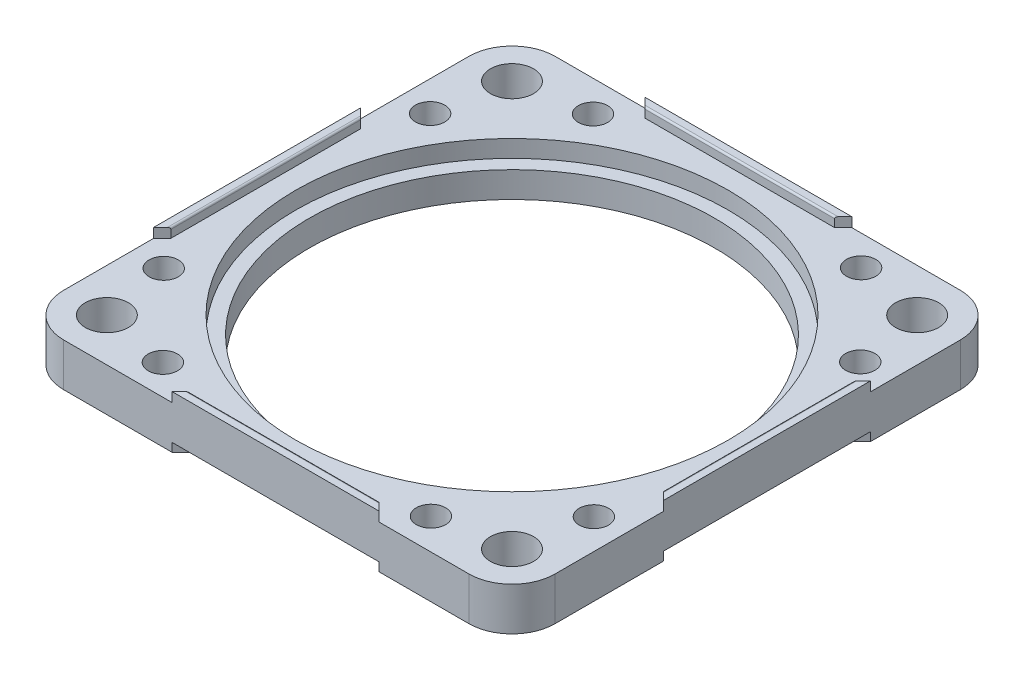
SolidWorks part; units mm, degrees
note: The reader was unsure of these and kept them because the rebuilt part matched: shared geometry of "Sketch5<3>".
material "PLA"
ref_plane "Front Plane" through (0, 0, 0) normal (0, 0, 1) x (1, 0, 0)
ref_plane "Top Plane" through (0, 0, 0) normal (0, 1, 0) x (1, 0, 0)
ref_plane "Right Plane" through (0, 0, 0) normal (1, 0, 0) x (0, 0, -1)
sketch "Sketch1" plane through (0, 0, 0) normal (0, 1, 0) x (1, 0, 0)
  line L1 (23.5, -28.5) -> (-23.5, -28.5)
  line L2 (28.5, -23.5) -> (28.5, 23.5)
  line L3 (23.5, 28.5) -> (-23.5, 28.5)
  line L4 (-28.5, -23.5) -> (-28.5, 23.5)
  line L5 (28.5, -28.5) -> (-28.5, 28.5) construction
  line L6 (28.5, 28.5) -> (-28.5, -28.5) construction
  arc A0 (28.5, -23.5) -> (23.5, -28.5) centre (23.5, -23.5) cw
  arc A1 (28.5, 23.5) -> (23.5, 28.5) centre (23.5, 23.5) ccw
  arc A2 (-28.5, 23.5) -> (-23.5, 28.5) centre (-23.5, 23.5) cw
  arc A3 (-28.5, -23.5) -> (-23.5, -28.5) centre (-23.5, -23.5) ccw
  point P0 (0, 0)
  dimension "D3" = 5
  dimension "D1" = 57
  dimension "D2" = 57
extrude "Boss-Extrude1" add sketch "Sketch1" along normal blind 5
sketch "Sketch2" plane through (0, 5, 0) normal (0, 1, 0) x (1, 0, 0)
  line L4 (28.5, -23.5) -> (28.5, 23.5)
  line L5 (23.5, 28.5) -> (-23.5, 28.5)
  line L6 (-28.5, 23.5) -> (-28.5, -23.5)
  line L7 (-23.5, -28.5) -> (23.5, -28.5)
  line L8 (28.5, -23.5) -> (28.5, 23.5)
  line L9 (23.5, 28.5) -> (-23.5, 28.5)
  line L10 (-28.5, 23.5) -> (-28.5, -23.5)
  line L11 (-23.5, -28.5) -> (23.5, -28.5)
  circle A0 centre (23.5, 23.5) radius 2.5
  circle A1 centre (15.5, 25) radius 1.7
  circle A2 centre (24.9, 15.5) radius 1.7
  arc A4 (23.5, -28.5) -> (28.5, -23.5) centre (23.5, -23.5) ccw
  arc A5 (28.5, 23.5) -> (23.5, 28.5) centre (23.5, 23.5) ccw
  arc A6 (-23.5, 28.5) -> (-28.5, 23.5) centre (-23.5, 23.5) ccw
  arc A7 (-28.5, -23.5) -> (-23.5, -28.5) centre (-23.5, -23.5) ccw
  arc A8 (23.5, -28.5) -> (28.5, -23.5) centre (23.5, -23.5) ccw
  arc A9 (28.5, 23.5) -> (23.5, 28.5) centre (23.5, 23.5) ccw
  arc A10 (-23.5, 28.5) -> (-28.5, 23.5) centre (-23.5, 23.5) ccw
  arc A11 (-28.5, -23.5) -> (-23.5, -28.5) centre (-23.5, -23.5) ccw
  dimension "D6" = 3.4
  dimension "D7" = 5
  dimension "D2" = 3.6
  dimension "D3" = 3.5
  dimension "D4" = 8
  dimension "D5" = 8
  dimension "D1" = 0
extrude "Cut-Extrude3" cut sketch "Sketch2" against normal blind 5 contours A2 | A1 | A0
sketch "Sketch5" plane through (0, 5, 0) normal (0, 1, 0) x (1, 0, 0)
  circle A0 centre (0, 0) radius 23.5
  circle A1 centre (0, 0) radius 25.1
  dimension "D1" = 47
  dimension "D2" = 50.2
extrude "Cut-Extrude5" cut sketch "Sketch5" against normal through all contours A0
extrude "Cut-Extrude6" cut sketch "Sketch5<3>" against normal blind 2
sketch "Sketch5<3>" plane through (0, 5, 0) normal (0, 1, 0) x (1, 0, 0) same geometry as "Sketch5"
sketch "Sketch6" plane through (0, 0, 0) normal (0, -1, 0) x (1, 0, 0)
  line L0 (28.5, 23.5) -> (28.5, -23.5) construction
  line L1 (22.15, -13.9123) -> (22.15, -17.0877)
  line L2 (22.15, -17.0877) -> (24.9, -18.6754)
  line L3 (24.9, -18.6754) -> (27.65, -17.0877)
  line L4 (27.65, -17.0877) -> (27.65, -13.9123)
  line L5 (27.65, -13.9123) -> (24.9, -12.3246)
  line L6 (24.9, -12.3246) -> (22.15, -13.9123)
  circle A0 centre (24.9, -15.5) radius 1.7 construction
  circle A1 centre (24.9, -15.5) radius 1.7
  circle A2 centre (24.9, -15.5) radius 2.75 construction
  dimension "D1" = 5.5
extrude "Cut-Extrude7" cut sketch "Sketch6" against normal blind 2.5
sketch "Sketch7" plane through (0, 5, 0) normal (0, 1, 0) x (1, 0, 0)
  line L0 (23.5, 28.5) -> (-23.5, 28.5) construction
  line L1 (23.5, 28.5) -> (-23.5, 28.5)
  line L2 (-1.0728, 0.2924) -> (-1.0728, 33.5294) construction
  line L3 (-12.0728, 27.5) -> (9.9272, 27.5)
  line L4 (9.9272, 27.5) -> (10.9272, 28.5)
  line L5 (-12.0728, 27.5) -> (-13.0728, 28.5)
  line L10 (28.5, -23.5) -> (28.5, 23.5)
  line L11 (23.5, 28.5) -> (-23.5, 28.5)
  line L12 (-28.5, 23.5) -> (-28.5, -23.5)
  line L13 (-23.5, -28.5) -> (23.5, -28.5)
  line L14 (28.5, -23.5) -> (28.5, 23.5)
  line L15 (23.5, 28.5) -> (-23.5, 28.5)
  line L16 (-28.5, 23.5) -> (-28.5, -23.5)
  line L17 (-23.5, -28.5) -> (23.5, -28.5)
  arc A4 (23.5, -28.5) -> (28.5, -23.5) centre (23.5, -23.5) ccw
  arc A5 (28.5, 23.5) -> (23.5, 28.5) centre (23.5, 23.5) ccw
  arc A6 (-23.5, 28.5) -> (-28.5, 23.5) centre (-23.5, 23.5) ccw
  arc A7 (-28.5, -23.5) -> (-23.5, -28.5) centre (-23.5, -23.5) ccw
  arc A8 (23.5, -28.5) -> (28.5, -23.5) centre (23.5, -23.5) ccw
  arc A9 (28.5, 23.5) -> (23.5, 28.5) centre (23.5, 23.5) ccw
  arc A10 (-23.5, 28.5) -> (-28.5, 23.5) centre (-23.5, 23.5) ccw
  arc A11 (-28.5, -23.5) -> (-23.5, -28.5) centre (-23.5, -23.5) ccw
  point P9 (-1.0728, 27.5)
  dimension "D1" = 135
  dimension "D2" = 11
  dimension "D3" = 1
  dimension "D4" = 0
extrude "Boss-Extrude2" add sketch "Sketch7" along normal blind 1.1 contours L3 L2 L15 L5 | L2 L3 L4 L1
sketch "Sketch8" plane through (0, 0, 0) normal (0, -1, 0) x (1, 0, 0)
  line L0 (9.9272, -27.5) -> (10.9272, -28.5) construction
  line L1 (-12.0728, -27.5) -> (9.9272, -27.5) construction
  line L2 (-12.0728, -27.5) -> (-13.0728, -28.5) construction
  line L3 (23.5, -28.5) -> (-23.5, -28.5) construction
  line L4 (-23.5, -28.5) -> (23.5, -28.5)
  line L5 (-28.5, 23.5) -> (-28.5, -23.5)
  line L6 (23.5, 28.5) -> (-23.5, 28.5)
  line L7 (28.5, -23.5) -> (28.5, 23.5)
  line L8 (-23.5, -28.5) -> (23.5, -28.5)
  line L9 (-28.5, 23.5) -> (-28.5, -23.5)
  line L10 (23.5, 28.5) -> (-23.5, 28.5)
  line L11 (28.5, -23.5) -> (28.5, 23.5)
  line L12 (9.9272, -27.5) -> (10.9272, -28.5)
  line L13 (-12.0728, -27.5) -> (9.9272, -27.5)
  line L14 (-12.0728, -27.5) -> (-13.0728, -28.5)
  line L15 (23.5, -28.5) -> (-23.5, -28.5)
  arc A4 (-28.5, -23.5) -> (-23.5, -28.5) centre (-23.5, -23.5) ccw
  arc A5 (-23.5, 28.5) -> (-28.5, 23.5) centre (-23.5, 23.5) ccw
  arc A6 (28.5, 23.5) -> (23.5, 28.5) centre (23.5, 23.5) ccw
  arc A7 (23.5, -28.5) -> (28.5, -23.5) centre (23.5, -23.5) ccw
  arc A8 (-28.5, -23.5) -> (-23.5, -28.5) centre (-23.5, -23.5) ccw
  arc A9 (-23.5, 28.5) -> (-28.5, 23.5) centre (-23.5, 23.5) ccw
  arc A10 (28.5, 23.5) -> (23.5, 28.5) centre (23.5, 23.5) ccw
  arc A11 (23.5, -28.5) -> (28.5, -23.5) centre (23.5, -23.5) ccw
  dimension "D1" = 0
extrude "Cut-Extrude8" cut sketch "Sketch8" against normal blind 1 contours L13 L14 L8 L12
pattern_circular "CirPattern9" count 4 over 360 about axis through (0, 0, 0) along (0, 1, 0) of "Cut-Extrude3", "Boss-Extrude2", "Cut-Extrude8", "Cut-Extrude7"
fillet "Fillet1" radius 0.2 4 edges at (-27.5, 6.1, 1.0728) (1.0728, 6.1, 27.5) (27.5, 6.1, -1.0728) (-1.0728, 6.1, -27.5)
